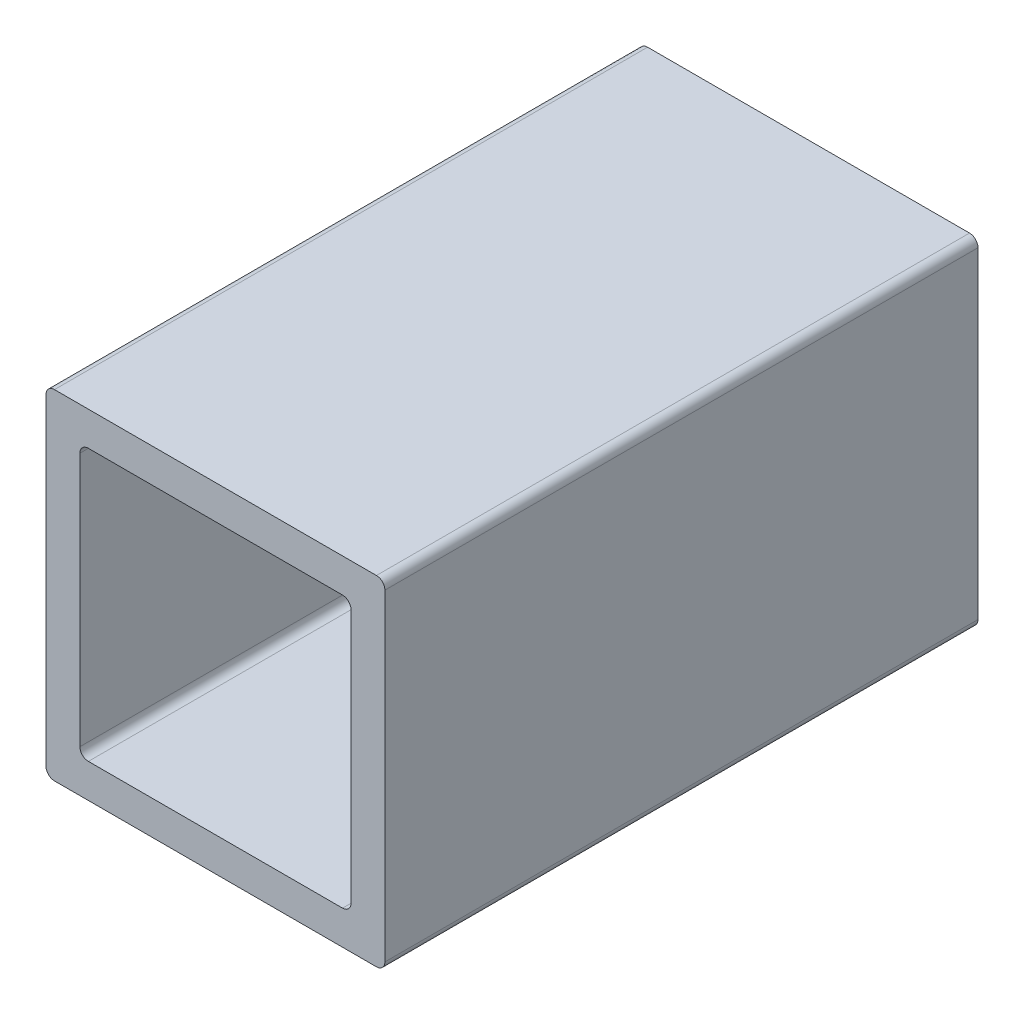
SolidWorks part; units mm, degrees
ref_plane "Plan de face" through (0, 0, 0) normal (0, 0, 1) x (1, 0, 0)
ref_plane "Plan de dessus" through (0, 0, 0) normal (0, 1, 0) x (1, 0, 0)
ref_plane "Plan de droite" through (0, 0, 0) normal (1, 0, 0) x (0, 0, -1)
sketch "Esquisse1" plane through (0, 0, 0) normal (0, 0, 1) x (1, 0, 0)
  line L0 (10, -10) -> (-10, 10) construction
  line L1 (-10, 10) -> (10, 10)
  line L2 (-10, 10) -> (-10, -10)
  line L3 (-10, -10) -> (10, -10)
  line L4 (10, 10) -> (10, -10)
  line L5 (10, 10) -> (-10, -10) construction
  dimension "D1" = 20
  dimension "D2" = 20
extrude "Boss.-Extru.1" add sketch "Esquisse1" along normal blind 35
shell "Coque2" thickness 2 removed face at (0, 0, 35)
fillet "Congé1" radius 0.5 8 edges at (8, 8, 18.5) (8, -8, 18.5) (-8, -8, 18.5) (-8, 8, 18.5) (-10, -10, 17.5) (10, -10, 17.5) (-10, 10, 17.5) (10, 10, 17.5)
